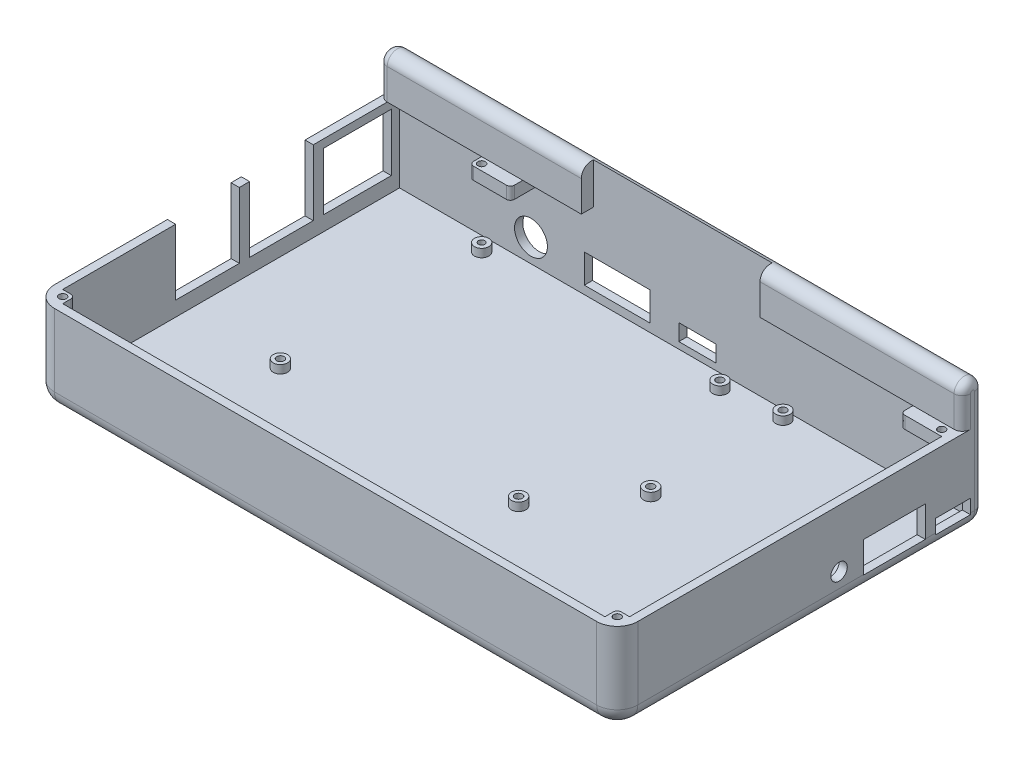
SolidWorks part; units mm, degrees
ref_plane "前视基准面" through (0, 0, 0) normal (0, 0, 1) x (1, 0, 0)
ref_plane "上视基准面" through (0, 0, 0) normal (0, 1, 0) x (1, 0, 0)
ref_plane "右视基准面" through (0, 0, 0) normal (1, 0, 0) x (0, 0, -1)
sketch "草图2" plane through (0, 0, 0) normal (0, 1, 0) x (1, 0, 0)
  line L1 (0, 0) -> (142, 0)
  line L2 (0, 0) -> (0, -89)
  line L3 (0, -89) -> (142, -89)
  line L4 (142, 0) -> (142, -89)
  dimension "D1" = 89
  dimension "D2" = 142
extrude "凸台-拉伸1" add sketch "草图2" along normal blind 21.6
shell "抽壳1" thickness 2 removed face at (71, 21.6, 44.5)
sketch "草图3" plane through (0, 2, 0) normal (0, 1, 0) x (1, 0, 0)
  line L0 (140, -87) -> (140, -2) construction
  line L1 (140, -2) -> (2, -2) construction
  line L2 (140, -87) -> (140, -2) construction
  line L3 (2, -2) -> (2, -87) construction
  circle A0 centre (132.6, -4.2) radius 1.75
  circle A1 centre (97.5, -4.1534) radius 1.75
  circle A2 centre (97.5, -36.3534) radius 1.75
  circle A3 centre (130, -36.3534) radius 1.75
  circle A4 centre (83.5, -5.5) radius 1.75
  circle A5 centre (25.5, -5.5) radius 1.75
  circle A6 centre (25.5, -54.5) radius 1.75
  circle A7 centre (83.5, -54.5) radius 1.75
  dimension "D3" = 3.5
  dimension "D9" = 58
  dimension "D1" = 7.4
  dimension "D2" = 2.2
  dimension "D4" = 35.1
  dimension "D5" = 32.2
  dimension "D6" = 10
  dimension "D7" = 23.5
  dimension "D8" = 3.5
  dimension "D10" = 49
extrude "凸台-拉伸2" add sketch "草图3" along normal blind 2
sketch "草图4" plane through (0, 4, 0) normal (0, 1, 0) x (1, 0, 0)
  circle A0 centre (132.5814, -4.2) radius 0.9
  circle A1 centre (132.6, -4.2) radius 1.75 construction
  circle A2 centre (97.5, -4.1534) radius 0.9
  circle A3 centre (97.5, -4.1534) radius 1.75 construction
  circle A5 centre (97.5, -36.3534) radius 0.9
  circle A6 centre (97.5, -36.3534) radius 1.75 construction
  circle A7 centre (130, -36.3534) radius 0.9
  circle A8 centre (130, -36.3534) radius 1.75 construction
  circle A9 centre (83.5, -5.5) radius 0.9
  circle A10 centre (83.5, -5.5) radius 1.75 construction
  circle A11 centre (25.5, -54.5) radius 0.9
  circle A13 centre (83.5, -54.5) radius 0.9
  circle A14 centre (25.5, -5.5) radius 0.7865
  circle A15 centre (25.5, -5.5) radius 1.75 construction
  dimension "D1" = 0
  dimension "D2" = 1.8
  dimension "D3" = 0
  dimension "D7" = 0
  dimension "D9" = 0
  dimension "D4" = 0
  dimension "D5" = 0
  dimension "D6" = 0
  dimension "D8" = 0
extrude "切除-拉伸1" cut sketch "草图4" against normal blind 3
sketch "草图6" plane through (0, 0, 0) normal (-1, 0, 0) x (0, 0, 1)
  line L0 (0, 0) -> (89, 0) construction
  line L1 (4, 19.6) -> (20.5, 19.6)
  line L2 (4, 19.6) -> (4, 5.6)
  line L3 (4, 5.6) -> (20.5, 5.6)
  line L4 (20.5, 19.6) -> (20.5, 5.6)
  line L5 (0, 21.6) -> (0, 0) construction
  line L7 (23, 21.6) -> (38.5, 21.6)
  line L8 (23, 21.6) -> (23, 5.6)
  line L9 (23, 5.6) -> (38.5, 5.6)
  line L10 (38.5, 21.6) -> (38.5, 5.6)
  line L12 (41, 21.6) -> (56.5, 21.6)
  line L13 (41, 21.6) -> (41, 5.6)
  line L14 (41, 5.6) -> (56.5, 5.6)
  line L15 (56.5, 21.6) -> (56.5, 5.6)
  dimension "D1" = 14
  dimension "D2" = 5.6
  dimension "D3" = 4
  dimension "D4" = 16.5
  dimension "D5" = 15.5
  dimension "37" = 23
  dimension "D6" = 5.6
  dimension "D7" = 16
  dimension "D8" = 2.5
extrude "切除-拉伸2" cut sketch "草图6" against normal blind 3
sketch "草图7" plane through (0, 0, 0) normal (0, 0, -1) x (-1, 0, 0)
  line L0 (0, 21.6) -> (0, 0) construction
  line L1 (-142, 0) -> (0, 0) construction
  line L9 (-63, 11) -> (-47, 11)
  line L10 (-63, 11) -> (-63, 4)
  line L11 (-63, 4) -> (-47, 4)
  line L12 (-47, 11) -> (-47, 4)
  line L13 (-79, 7.6) -> (-70, 7.6)
  line L14 (-79, 7.6) -> (-79, 3.6)
  line L15 (-79, 3.6) -> (-70, 3.6)
  line L16 (-70, 7.6) -> (-70, 3.6)
  circle A0 centre (-34, 7.6) radius 4
  dimension "D2" = 8
  dimension "D1" = 34
  dimension "D3" = 7.6
  dimension "D4" = 4
  dimension "D5" = 47
  dimension "D6" = 7
  dimension "D7" = 16
  dimension "D8" = 70
  dimension "D9" = 3.6
  dimension "D10" = 4
  dimension "D11" = 9
extrude "切除-拉伸3" cut sketch "草图7" against normal blind 10
sketch "草图8" plane through (142, 0, 0) normal (1, 0, 0) x (0, 0, -1)
  line L0 (0, 21.6) -> (0, 0) construction
  line L1 (-11.5, 7.1) -> (-3, 7.1)
  line L2 (-11.5, 7.1) -> (-11.5, 3.6)
  line L3 (-11.5, 3.6) -> (-3, 3.6)
  line L4 (-3, 7.1) -> (-3, 3.6)
  line L5 (-89, 0) -> (0, 0) construction
  line L7 (-29, 11.4) -> (-14, 11.4)
  line L8 (-29, 11.4) -> (-29, 3.9)
  line L9 (-29, 3.9) -> (-14, 3.9)
  line L10 (-14, 11.4) -> (-14, 3.9)
  circle A0 centre (-35, 7.6) radius 2
  dimension "D10" = 4
  dimension "D1" = 3
  dimension "D2" = 3.6
  dimension "D3" = 8.5
  dimension "D4" = 3.5
  dimension "D5" = 14
  dimension "D6" = 7.5
  dimension "D7" = 15
  dimension "D8" = 3.9
  dimension "D9" = 35
  dimension "D11" = 7.6
extrude "切除-拉伸4" cut sketch "草图8" against normal blind 5.8412
ref_plane "基准面1" through (0, 21.6, 0) normal (0, 1, 0) x (1, 0, 0)
sketch "草图9" plane through (0, 21.6, 0) normal (0, 1, 0) x (1, 0, 0)
  line L0 (142, -89) -> (142, 0) construction
  line L1 (0, 0) -> (142, 0)
  line L2 (0, 0) -> (0, -5)
  line L3 (0, -5) -> (142, -5)
  line L4 (142, 0) -> (142, -5)
  dimension "D1" = 5
extrude "凸台-拉伸3" add sketch "草图9" along normal blind 10
fillet "圆角1" 2 edges at (71, 31.6, 0) (71, 31.6, 5) type full round first side face at (30, 7.6, 0) second side face at (71, 24.9333, 5) middle face at (71, 31.6, 2.5)
fillet "圆角2" radius 5 1 edges at (0, 10.8, 89)
fillet "圆角3" radius 5 1 edges at (142, 10.8, 89)
fillet "圆角4" radius 4 6 edges at (1.4645, 0, 87.5355) (140.5355, 0, 87.5355) (142, 0, 42) (71, 0, 0) (0, 0, 42) (71, 0, 89)
fillet "圆角6" radius 2 8 edges at (142, 25.35, 5) (142, 31.6, 2.5) (140.8284, 1.1716, 1.1716) (142, 16.55, 0) (0, 25.35, 5) (0, 31.6, 2.5) (1.1716, 1.1716, 1.1716) (0, 16.55, 0)
sketch "草图10" plane through (0, 21.6, 0) normal (0, 1, 0) x (1, 0, 0)
  line L0 (2, -2.5) -> (49.25, -2.5) construction
  line L1 (49.25, -2) -> (92.75, -2)
  line L2 (49.25, -2) -> (49.25, -5)
  line L3 (49.25, -5) -> (92.75, -5)
  line L4 (92.75, -2) -> (92.75, -5)
  line L5 (2, 0) -> (2, -5) construction
  line L6 (140, -2.5) -> (92.75, -2.5) construction
  line L7 (2, 0) -> (140, 0) construction
  line L8 (140, -5) -> (140, 0) construction
  dimension "D1" = 3
  dimension "D2" = 2
  dimension "D3" = 43.5
extrude "切除-拉伸5" cut sketch "草图10" along normal blind 24
ref_plane "基准面2" through (0, 18.6, 0) normal (0, 1, 0) x (1, 0, 0)
sketch "草图12" plane through (0, 18.6, 0) normal (0, 1, 0) x (1, 0, 0)
  line L1 (2, -87) -> (5, -87)
  line L2 (2, -87) -> (2, -84)
  line L3 (2, -84) -> (5, -84)
  line L4 (5, -87) -> (5, -84)
  line L5 (140, -87) -> (137, -87)
  line L6 (140, -87) -> (140, -84)
  line L7 (140, -84) -> (137, -84)
  line L8 (137, -87) -> (137, -84)
  dimension "D1" = 3
  dimension "D2" = 3
  dimension "D3" = 3
  dimension "D4" = 3
extrude "凸台-拉伸8" add sketch "草图12" along normal up to surface (3 mm away) up to face at (71.0414, 21.6, 64.3485)
sketch "草图13" plane through (0, 18.6, 0) normal (0, 1, 0) x (1, 0, 0)
  line L0 (140, -87) -> (140, -2) construction
  line L1 (140, -5.001) -> (130, -5.001)
  line L2 (140, -5.001) -> (140, -8.001)
  line L3 (140, -8.001) -> (130, -8.001)
  line L4 (130, -5.001) -> (130, -8.001)
  line L5 (92.75, -5) -> (140, -5) construction
  line L6 (49.25, -2) -> (92.75, -2) construction
  line L7 (25, -2) -> (35, -2)
  line L8 (25, -2) -> (25, -8.001)
  line L9 (25, -8.001) -> (35, -8.001)
  line L10 (35, -2) -> (35, -8.001)
  line L11 (0, -3) -> (0, -23) construction
  dimension "D1" = 0.001
  dimension "D2" = 10
  dimension "D3" = 3
  dimension "D4" = 10
  dimension "D5" = 25
extrude "凸台-拉伸9" add sketch "草图13" along normal blind 3
sketch "草图14" plane through (0, 18.6, 0) normal (0, 1, 0) x (1, 0, 0)
  line L0 (5, -87) -> (5, -84) construction
  line L1 (5, -84) -> (2, -84) construction
  line L2 (140, -84) -> (137, -84) construction
  line L4 (130, -8.001) -> (140, -8.001) construction
  line L5 (140, -87) -> (140, -2) construction
  line L7 (137, -84) -> (137, -87) construction
  line L8 (25, -5) -> (25, -8.001) construction
  line L9 (25, -8.001) -> (35, -8.001) construction
  circle A0 centre (3.5, -85.5) radius 0.9
  circle A1 centre (138.5, -85.5) radius 0.9
  circle A2 centre (138.5, -6.501) radius 0.9
  circle A3 centre (26.5, -6.501) radius 0.9
  dimension "D1" = 1.8
  dimension "D4" = 1.5
  dimension "D5" = 1.5
  dimension "D8" = 1.8
  dimension "D2" = 1.5
  dimension "D3" = 1.5
  dimension "D6" = 1.5
  dimension "D7" = 1.5
  dimension "D9" = 1.5
  dimension "D10" = 1.5
extrude "切除-拉伸6" cut sketch "草图14" along normal blind 10
fillet "圆角11" radius 1 5 edges at (137, 20.1, 84) (130, 20.1, 8.001) (35, 20.1, 8.001) (25, 20.1, 8.001) (5, 20.1, 84)
